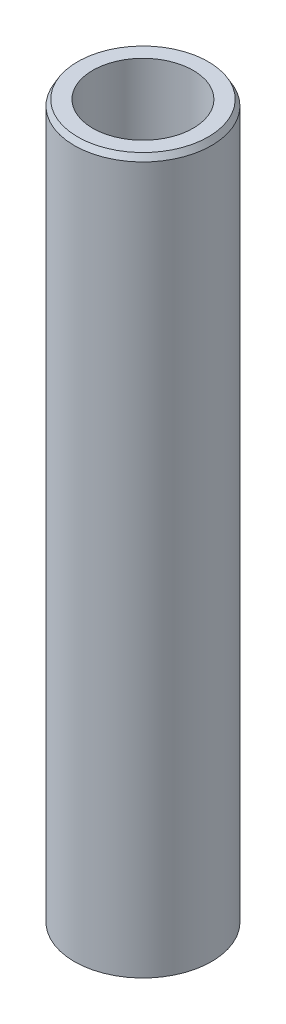
SolidWorks part; units mm, degrees
ref_plane "Front Plane" through (0, 0, 0) normal (0, 0, 1) x (1, 0, 0)
ref_plane "Top Plane" through (0, 0, 0) normal (0, 1, 0) x (1, 0, 0)
ref_plane "Right Plane" through (0, 0, 0) normal (1, 0, 0) x (0, 0, -1)
sketch "Sketch1" plane through (0, 0, 0) normal (0, 1, 0) x (1, 0, 0)
  circle A0 centre (0, 0) radius 57.5
  dimension "SHAFT_OD" = 115
extrude "Boss-Extrude1" add sketch "Sketch1" along normal blind 600
sketch "Sketch2" plane through (0, 0, 0) normal (0, 1, 0) x (1, 0, 0)
  circle A0 centre (0, 0) radius 42.0865
  dimension "BORE_D" = 84.1729
extrude "Cut-Extrude1" cut sketch "Sketch2" along normal through all
chamfer "Chamfer1" distance 4.8586 angle 30 2 edges at (0, 600, 57.5) (0, 0, 57.5) first distance on face at (0, 600, 57.5) first distance on face at (0, 0, 42.0865)
